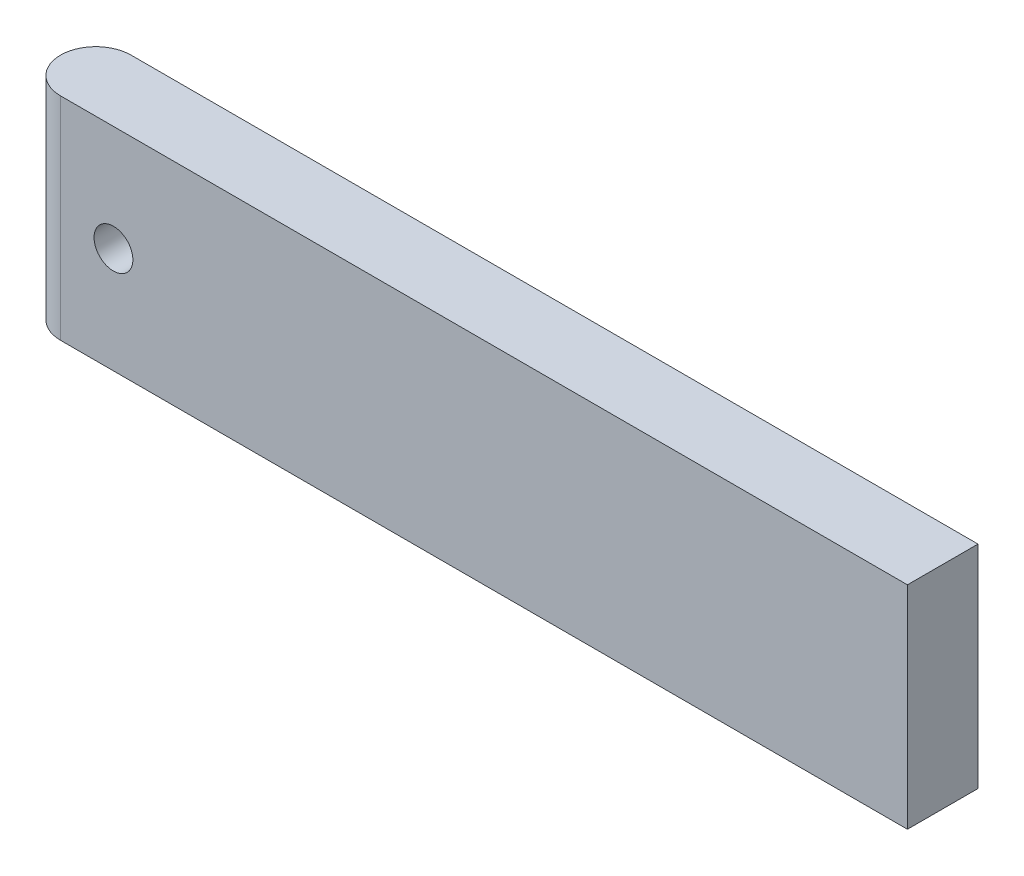
SolidWorks part; units mm, degrees
ref_plane "Front Plane" through (0, 0, 0) normal (0, 0, 1) x (1, 0, 0)
ref_plane "Top Plane" through (0, 0, 0) normal (0, 1, 0) x (1, 0, 0)
ref_plane "Right Plane" through (0, 0, 0) normal (1, 0, 0) x (0, 0, -1)
sketch "Sketch1" plane through (0, 0, 0) normal (0, 0, 1) x (1, 0, 0)
  line L1 (5, -6) -> (-5, -6)
  line L2 (5, -6) -> (5, 6)
  line L3 (5, 6) -> (-5, 6)
  line L4 (-5, -6) -> (-5, 6)
  line L5 (0, 6) -> (0, -6) construction
  line L6 (5, 0) -> (-5, 0) construction
  circle A0 centre (0, 0) radius 1.1
  point P0 (0, 0)
  dimension "D2" = 2.2
  dimension "D1" = 10
  dimension "D3" = 12
extrude "Boss-Extrude1" add sketch "Sketch1" along normal blind 4
fillet "Fillet1" radius 2 2 edges at (-5, 0, 4) (-5, 0, 0)
sketch "Sketch2" plane through (5, 0, 0) normal (1, 0, 0) x (0, 0, -1)
  line L4 (0, -6) -> (0, 6)
  line L5 (0, 6) -> (-4, 6)
  line L6 (-4, 6) -> (-4, -6)
  line L7 (-4, -6) -> (0, -6)
  line L8 (0, -6) -> (0, 6)
  line L9 (0, 6) -> (-4, 6)
  line L10 (-4, 6) -> (-4, -6)
  line L11 (-4, -6) -> (0, -6)
  dimension "D1" = 0
extrude "Boss-Extrude2" add sketch "Sketch2" along normal blind 40
